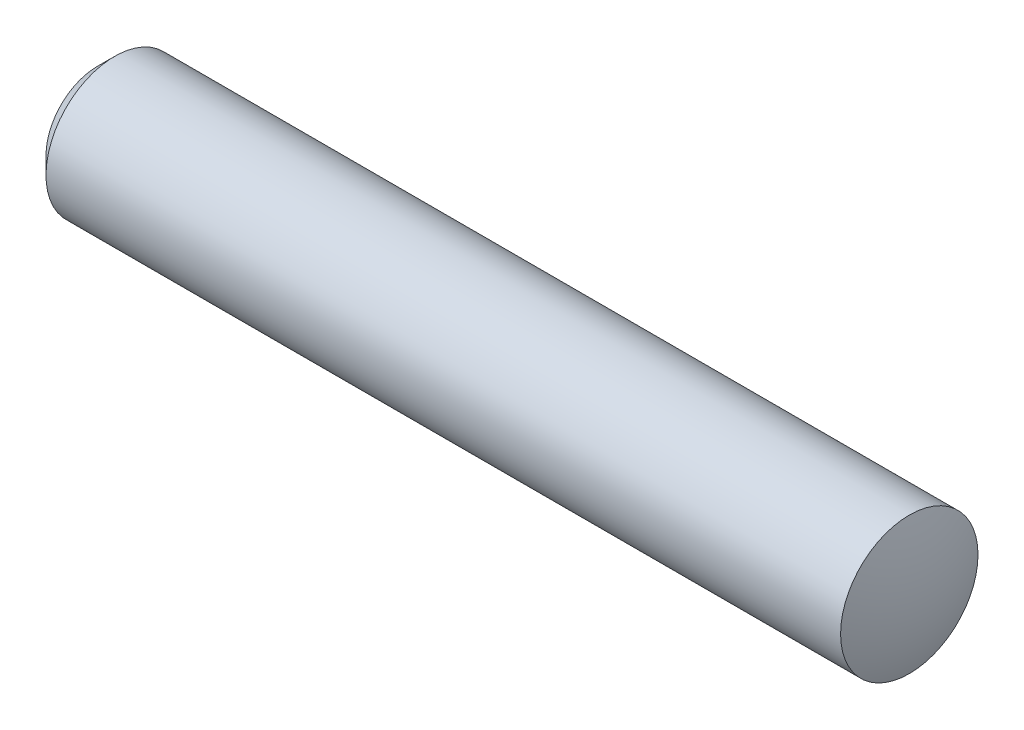
SolidWorks part; units mm, degrees
ref_plane "Front" through (0, 0, 0) normal (0, 0, 1) x (1, 0, 0)
ref_plane "Top" through (0, 0, 0) normal (0, 1, 0) x (1, 0, 0)
ref_plane "Right" through (0, 0, 0) normal (1, 0, 0) x (0, 0, -1)
sketch "Sketch1" plane through (0, 0, 0) normal (0, 0, 1) x (1, 0, 0)
  line L0 (-11.8977, 0) -> (11.8977, 0) construction
  line L1 (-12.1023, 1.5) -> (-11.6023, 2)
  line L2 (-11.6023, 2) -> (-6.1023, 2)
  line L3 (11.8977, 0) -> (11.8977, -7.427) construction
  line L4 (-11.8977, 0) -> (-11.8977, -2.1222) construction
  line L5 (-6.1023, 2) -> (-2.1023, 2)
  line L6 (-2.1023, 2) -> (11.5284, 2)
  line L7 (-7.8682, 16.2978) -> (10.1318, 16.2978) construction
  line L8 (-11.8977, 0) -> (-2.1023, 0)
  line L9 (-4.1023, 2) -> (-4.1023, 0) construction
  line L10 (-12.1023, 1.5) -> (-6.1023, 1.5) construction
  line L11 (-6.1023, 1.5) -> (-6.1023, 2) construction
  line L12 (-2.1023, 0) -> (11.8977, 0)
  line L13 (4.8977, 0) -> (4.8977, -0.4) construction
  line L14 (-9.1023, 1.5) -> (-9.1023, -0.4) construction
  line L15 (-9.1023, -0.4) -> (4.8977, -0.4) construction
  arc A0 (11.5284, 2) -> (11.8977, 0) centre (6.2977, 0) cw
  arc A1 (-12.1023, 1.5) -> (-11.8977, 0) centre (-17.4977, 0) cw
  arc A2 (-11.8977, -0.8204) -> (11.5284, -1.6339) centre (-2.1023, -56.45) cw construction
  dimension "D1" = 0.5
  dimension "D2" = 45
revolve "Revolve1" add sketch "Sketch1" angle 360 about L8
cosmetic thread "Cosmetic Thread1" [suppressed] parameters "D1"=6, "D2"=3
cosmetic thread "Cosmetic Thread2" [suppressed] parameters "D1"=14, "D2"=3
sketch "Sketch2" plane through (0, 0, 0) normal (0, 0, 1) x (1, 0, 0)
  line L0 (11.5284, 1.5) -> (11.817, 2)
  line L1 (11.817, 2) -> (11.817, 2.5774)
  line L2 (11.817, 2.5774) -> (11.2397, 2.5774)
  line L3 (11.2397, 2.5774) -> (11.2397, 2)
  line L4 (11.2397, 2) -> (11.5284, 1.5)
  line L5 (11.5284, -2) -> (11.5284, 2) construction
  line L6 (0, 0) -> (13.194, 0) construction
  line L7 (-2.1023, 2) -> (11.5284, 2) construction
  dimension "D1" = 3
revolve "Cut-Revolve1" [suppressed] cut sketch "Sketch2" angle 360 about L6
pattern_linear "LPattern1" [suppressed] count 18 along (-1, 0, 0) of bodies 143
sketch "Sketch3" plane through (0, 0, 0) normal (0, 0, 1) x (1, 0, 0)
  line L0 (0, 0) -> (-12.6753, 0) construction
  line L1 (-11.6023, 1.5) -> (-11.3136, 2)
  line L2 (-11.3136, 2) -> (-11.3136, 2.5774)
  line L3 (-11.3136, 2.5774) -> (-11.891, 2.5774)
  line L4 (-11.891, 2.5774) -> (-11.891, 2)
  line L5 (-11.891, 2) -> (-11.6023, 1.5)
  line L6 (-11.6023, 2) -> (-6.1023, 2) construction
  line L7 (-11.6023, -2) -> (-11.6023, 2) construction
  dimension "D1" = 3
revolve "Cut-Revolve2" [suppressed] cut sketch "Sketch3" angle 360 about L0
pattern_linear "LPattern2" [suppressed] count 8 spacing 0.8 along (1, 0, 0) of bodies 145
equation "\"la@Sketch1\" = \"l@Sketch1\" - \"b@Sketch1\""
equation "\"F@Sketch1\" = \"d@Sketch1\" / 10"
equation "\"D1@Cosmetic Thread1\" = \"bm@Sketch1\""
equation "\"D1@Cosmetic Thread2\" = \"b@Sketch1\""
equation "\"D1@Sketch2\" = \"D2@Cosmetic Thread2\""
equation "\"D1@LPattern1\" = \"b@Sketch1\" / \"p@LPattern1\""
equation "\"D1@Sketch3\" = \"D2@Cosmetic Thread1\""
equation "\"D1@LPattern2\" = \"bm@Sketch1\" / \"D3@LPattern2\""
